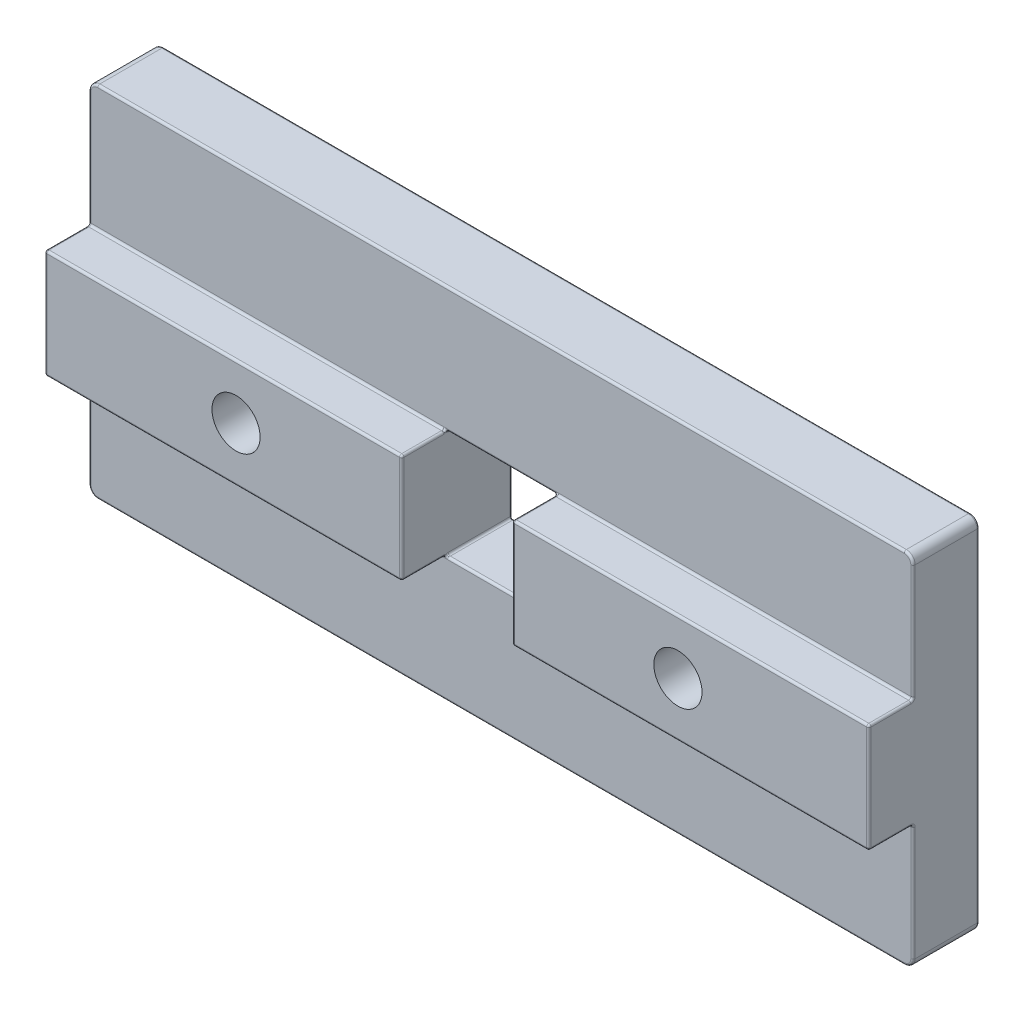
SolidWorks part; units mm, degrees
ref_plane "Front Plane" through (0, 0, 0) normal (0, 0, 1) x (1, 0, 0)
ref_plane "Top Plane" through (0, 0, 0) normal (0, 1, 0) x (1, 0, 0)
ref_plane "Right Plane" through (0, 0, 0) normal (1, 0, 0) x (0, 0, -1)
sketch "Sketch1" plane through (0, 0, 0) normal (0, 0, 1) x (1, 0, 0)
  line L1 (23.6855, -10.3124) -> (-23.6855, -10.3124)
  line L2 (23.6855, -10.3124) -> (23.6855, 10.3124)
  line L3 (23.6855, 10.3124) -> (-23.6855, 10.3124)
  line L4 (-23.6855, -10.3124) -> (-23.6855, 10.3124)
  line L5 (23.6855, -10.3124) -> (-23.6855, 10.3124) construction
  line L6 (23.6855, 10.3124) -> (-23.6855, -10.3124) construction
  line L7 (-3.1623, 3.1242) -> (3.1877, 3.1242)
  line L8 (-3.1623, 3.1242) -> (-3.1623, -3.1242)
  line L9 (-3.1623, -3.1242) -> (3.1877, -3.1242)
  line L10 (3.1877, 3.1242) -> (3.1877, -3.1242)
  circle A0 centre (-12.6873, 0) radius 1.3843
  circle A1 centre (12.7127, 0) radius 1.3843
  point P0 (0, 0)
  dimension "Mounting Hole Diameter" = 2.7686
  dimension "Length" = 47.371
  dimension "Width" = 20.6248
  dimension "Mounting Hole from Edge Horiz" = 10.9982
  dimension "Mounting Hole to Cutout" = 9.525
  dimension "Cutout Length" = 6.35
  dimension "Mounting Hole from Edge Vert" = 10.3124
  dimension "Mounting Hole Center-to-Center" = 25.4
  dimension "Cutout from Edge" = 7.1882
  dimension "Cutout Width" = 6.2484
sketch "Sketch2" plane through (0, 0, 0) normal (1, 0, 0) x (0, 0, -1)
  line L0 (3.81, 10.3124) -> (-2.54, 10.3124) construction
  line L1 (3.81, 3.1242) -> (0, 3.1242) construction
  line L2 (0, 3.1242) -> (-2.54, 3.1242) construction
  line L3 (0, -10.3124) -> (3.81, -10.3124) construction
  point P7 (0, 10.3124)
  dimension "Thickness" = 6.35
  dimension "Body Thickness" = 3.81
sketch "Sketch3" plane through (0, 0, 0) normal (0, 0, 1) x (1, 0, 0)
  line L1 (-23.6855, 10.3124) -> (23.6855, 10.3124)
  line L2 (-23.6855, 10.3124) -> (-23.6855, -10.3124)
  line L3 (-23.6855, -10.3124) -> (23.6855, -10.3124)
  line L4 (23.6855, 10.3124) -> (23.6855, -10.3124)
extrude "Boss-Extrude1" add sketch "Sketch3" against normal up to vertex (3.81 mm away) up to point (0, 10.3124, -3.81)
sketch "Sketch4" plane through (0, 0, 0) normal (0, 0, 1) x (1, 0, 0)
  line L0 (-23.6855, -10.3124) -> (-23.6855, 10.3124) construction
  line L1 (-23.6855, 3.1242) -> (23.6855, 3.1242)
  line L2 (-23.6855, 3.1242) -> (-23.6855, -3.1242)
  line L3 (-23.6855, -3.1242) -> (23.6855, -3.1242)
  line L4 (23.6855, 3.1242) -> (23.6855, -3.1242)
  line L5 (23.6855, -10.3124) -> (23.6855, 10.3124) construction
  line L6 (-3.1623, -3.1242) -> (3.1877, -3.1242) construction
  line L7 (-3.1623, 3.1242) -> (3.1877, 3.1242) construction
extrude "Boss-Extrude2" add sketch "Sketch4" along normal up to vertex (2.54 mm away) up to point (0, 10.3124, 2.54)
sketch "Sketch5" plane through (0, 0, 0) normal (0, 0, 1) x (1, 0, 0)
  line L0 (-3.1623, 3.1242) -> (-3.1623, -3.1242) construction
  line L1 (-3.1623, 3.1242) -> (3.1877, 3.1242)
  line L2 (-3.1623, 3.1242) -> (-3.1623, -3.1242)
  line L3 (-3.1623, -3.1242) -> (3.1877, -3.1242)
  line L4 (3.1877, 3.1242) -> (3.1877, -3.1242)
  line L5 (-3.1623, 3.1242) -> (3.1877, 3.1242) construction
  circle A0 centre (-12.6873, 0) radius 1.3843
  circle A1 centre (12.7127, 0) radius 1.3843
  circle A2 centre (-12.6873, 0) radius 1.3843 construction
  circle A3 centre (12.7127, 0) radius 1.3843 construction
extrude "Cut-Extrude1" cut sketch "Sketch5" against normal through all both and the other way through all
fillet "Fillet5" radius 0.508 4 edges at (-23.6855, -10.3124, -1.905) (23.6855, -10.3124, -1.905) (-23.6855, 10.3124, -1.905) (23.6855, 10.3124, -1.905)
fillet "Fillet1" radius 0.127 36 edges at (-23.6855, 3.1242, 1.27) (-23.6855, 0, 2.54) (-23.6855, -3.1242, 1.27) (-23.6855, -6.4643, 0) (-23.6855, 0, -3.81) (-23.6855, 6.4643, 0) (23.6855, -3.1242, 1.27) (23.6855, 0, 2.54) (23.6855, 3.1242, 1.27) (23.6855, 6.4643, 0) (23.6855, 0, -3.81) (23.6855, -6.4643, 0) (0.0127, 3.1242, -3.81) (3.1877, 0, -3.81) (0.0127, -3.1242, -3.81) (-3.1623, 0, -3.81) (-13.4239, -3.1242, 0) (-13.4239, 3.1242, 0) (13.4366, -3.1242, 0) (0, 10.3124, 0) (0, 10.3124, -3.81) (0, -10.3124, -3.81) (0, -10.3124, 0) (13.4366, 3.1242, 0) (13.4366, -3.1242, 2.54) (-13.4239, -3.1242, 2.54) (13.4366, 3.1242, 2.54) (-13.4239, 3.1242, 2.54) (23.5367, 10.1636, 0) (-23.5367, 10.1636, 0) (-23.5367, -10.1636, -3.81) (-23.5367, 10.1636, -3.81) (23.5367, 10.1636, -3.81) (23.5367, -10.1636, -3.81) (-23.5367, -10.1636, 0) (23.5367, -10.1636, 0)
fillet "Fillet2" radius 0.127 14 edges at (3.1877, 3.1614, 0.0372) (3.1877, -3.1614, 0.0372) (3.1877, -3.1242, 1.27) (3.1877, -3.087, 2.5028) (3.1877, 0, 2.54) (3.1877, 3.087, 2.5028) (-3.1623, 3.1614, 0.0372) (-3.1623, -3.1614, 0.0372) (-3.1623, -3.1242, 1.27) (-3.1623, -3.087, 2.5028) (-3.1623, 0, 2.54) (-3.1623, 3.087, 2.5028) (3.1877, 3.1242, 1.27) (-3.1623, 3.1242, 1.27)
fillet "Fillet3" radius 0.127 2 edges at (0.0127, -3.1242, 0) (0.0127, 3.1242, 0)
fillet "Fillet4" radius 0.1245 16 edges at (-3.1995, -3.1614, -3.7728) (-3.1781, -3.1575, -0.0413) (-3.1623, -3.1252, -0.111) (3.2249, -3.1614, -3.7728) (3.2035, -3.1575, -0.0413) (3.1877, -3.1252, -0.111) (3.2249, 3.1614, -3.7728) (3.2035, 3.1575, -0.0413) (3.1877, 3.1252, -0.111) (-3.1995, 3.1614, -3.7728) (-3.1781, 3.1575, -0.0413) (-3.1623, 3.1252, -0.111) (-3.1623, -3.1242, -1.905) (3.1877, -3.1242, -1.905) (3.1877, 3.1242, -1.905) (-3.1623, 3.1242, -1.905)
